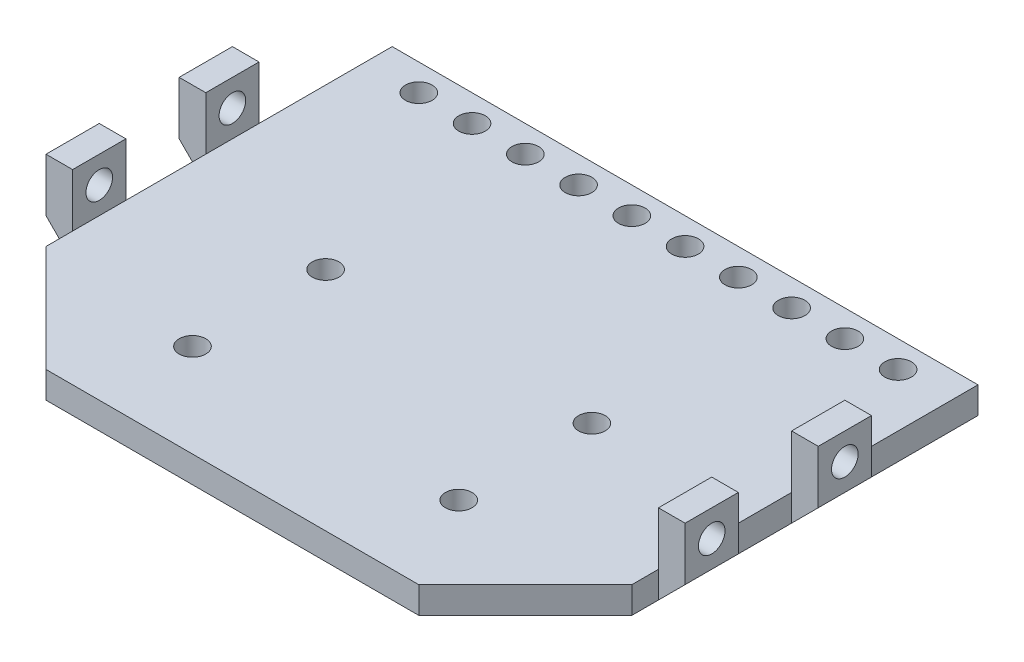
SolidWorks part; units mm, degrees
ref_plane "Front Plane" through (0, 0, 0) normal (0, 0, 1) x (1, 0, 0)
ref_plane "Top Plane" through (0, 0, 0) normal (0, 1, 0) x (1, 0, 0)
ref_plane "Right Plane" through (0, 0, 0) normal (1, 0, 0) x (0, 0, -1)
sketch "Sketch1" plane through (0, 0, 0) normal (0, 1, 0) x (1, 0, 0)
  line L1 (-60, 42.5) -> (60, 42.5)
  line L2 (-60, 42.5) -> (-60, -42.5)
  line L3 (-60, -42.5) -> (60, -42.5)
  line L4 (60, 42.5) -> (60, -42.5)
  line L5 (-60, 42.5) -> (60, -42.5) construction
  line L6 (-60, -42.5) -> (60, 42.5) construction
  point P0 (0, 0)
  dimension "D1" = 120
  dimension "D2" = 85
extrude "Boss-Extrude1" add sketch "Sketch1" along normal blind 5
sketch "Sketch2" plane through (0, 5, 0) normal (0, 1, 0) x (1, 0, 0)
  line L0 (-60, 42.5) -> (-60, -42.5) construction
  line L1 (-60, 17.5) -> (-55, 17.5)
  line L2 (-60, 17.5) -> (-60, 7.5)
  line L3 (-60, 7.5) -> (-55, 7.5)
  line L4 (-55, 17.5) -> (-55, 7.5)
  line L6 (-60, -7.5) -> (-55, -7.5)
  line L7 (-60, -7.5) -> (-60, -17.5)
  line L8 (-60, -17.5) -> (-55, -17.5)
  line L9 (-55, -7.5) -> (-55, -17.5)
  line L10 (-60, 12.5) -> (-55, 12.5) construction
  line L11 (-60, -12.5) -> (-55, -12.5) construction
  line L14 (60, 42.5) -> (-60, 42.5) construction
  line L16 (0, 0) -> (0, -27.3364) construction
  line L17 (60, -12.5) -> (55, -12.5) construction
  line L18 (60, 12.5) -> (55, 12.5) construction
  line L19 (55, -7.5) -> (55, -17.5)
  line L20 (60, -17.5) -> (55, -17.5)
  line L21 (60, -7.5) -> (60, -17.5)
  line L22 (60, -7.5) -> (55, -7.5)
  line L23 (55, 17.5) -> (55, 7.5)
  line L24 (60, 7.5) -> (55, 7.5)
  line L25 (60, 17.5) -> (60, 7.5)
  line L26 (60, 17.5) -> (55, 17.5)
  dimension "D1" = 30
  dimension "D2" = 10
  dimension "D3" = 10
  dimension "D4" = 25
  dimension "D5" = 5
  dimension "D6" = 5
extrude "Boss-Extrude2" add sketch "Sketch2" along normal blind 10
sketch "Sketch3" plane through (-60, 0, 0) normal (-1, 0, 0) x (0, 0, 1)
  line L0 (7.5, 15) -> (17.5, 15) construction
  line L1 (-17.5, 15) -> (-7.5, 15) construction
  line L2 (-17.5, 15) -> (-17.5, 5) construction
  line L3 (7.5, 15) -> (7.5, 5) construction
  circle A0 centre (-12.5, 10) radius 2.5
  circle A1 centre (12.5, 10) radius 2.5
  dimension "D1" = 5
  dimension "D2" = 5
  dimension "D3" = 5
  dimension "D4" = 5
  dimension "D5" = 5
  dimension "D6" = 5
extrude "Cut-Extrude1" cut sketch "Sketch3" against normal through all
sketch "Sketch5" plane through (0, 5, 0) normal (0, 1, 0) x (1, 0, 0)
  line L0 (0, 0) -> (0, -37.502) construction
  line L1 (-60, 42.5) -> (-55, 42.5)
  line L2 (-60, 42.5) -> (-60, 17.5)
  line L3 (-60, 17.5) -> (-55, 17.5)
  line L4 (-55, 42.5) -> (-55, 17.5)
  line L5 (-60, 7.5) -> (-55, 7.5)
  line L6 (-60, 7.5) -> (-60, -7.5)
  line L7 (-60, -7.5) -> (-55, -7.5)
  line L8 (-55, 7.5) -> (-55, -7.5)
  line L9 (-55, -17.5) -> (-60, -17.5)
  line L10 (-55, -17.5) -> (-55, -42.5)
  line L11 (-55, -42.5) -> (-60, -42.5)
  line L12 (-60, -17.5) -> (-60, -42.5)
  line L13 (60, -17.5) -> (60, -42.5)
  line L14 (55, -42.5) -> (60, -42.5)
  line L15 (55, -17.5) -> (55, -42.5)
  line L16 (55, -17.5) -> (60, -17.5)
  line L17 (55, 7.5) -> (55, -7.5)
  line L18 (60, -7.5) -> (55, -7.5)
  line L19 (60, 7.5) -> (60, -7.5)
  line L20 (60, 7.5) -> (55, 7.5)
  line L21 (55, 42.5) -> (55, 17.5)
  line L22 (60, 17.5) -> (55, 17.5)
  line L23 (60, 42.5) -> (60, 17.5)
  line L24 (60, 42.5) -> (55, 42.5)
extrude "Cut-Extrude2" cut sketch "Sketch5" against normal through all
chamfer "Chamfer1" distance 5 angle 45 4 edges at (-60, 0, 12.5) (-60, 0, -12.5) (60, 0, -12.5) (60, 0, 12.5)
sketch "Sketch6" plane through (0, 0, 0) normal (0, -1, 0) x (1, 0, 0)
  line L0 (-55, 42.5) -> (55, 42.5) construction
  circle A0 centre (25, 0) radius 2.5
  circle A1 centre (-25, 0) radius 2.5
  circle A2 centre (25, 25) radius 2.5
  circle A3 centre (-25, 25) radius 2.5
  dimension "D1" = 5
  dimension "D2" = 5
  dimension "D3" = 25
  dimension "D4" = 25
  dimension "D5" = 42.5
  dimension "D6" = 42.5
  dimension "D7" = 2
extrude "Cut-Extrude3" cut sketch "Sketch6" against normal through all
sketch "Sketch7" plane through (0, 0, 0) normal (0, -1, 0) x (1, 0, 0)
  line L0 (55, -42.5) -> (-55, -42.5) construction
  line L1 (-55, -17.5) -> (-55, -42.5) construction
  line L3 (55, -42.5) -> (55, -17.5) construction
  circle A0 centre (-45, -37.5) radius 2.5
  circle A1 centre (-35, -37.5) radius 2.5
  circle A2 centre (-25, -37.5) radius 2.5
  circle A3 centre (-15, -37.5) radius 2.5
  circle A4 centre (-5, -37.5) radius 2.5
  circle A5 centre (5, -37.5) radius 2.5
  circle A6 centre (15, -37.5) radius 2.5
  circle A7 centre (25, -37.5) radius 2.5
  circle A8 centre (35, -37.5) radius 2.5
  circle A9 centre (45, -37.5) radius 2.5
  dimension "D1" = 5
  dimension "D2" = 5
  dimension "D3" = 10
  dimension "D5" = 10
  dimension "D4" = 10
extrude "Cut-Extrude4" cut sketch "Sketch7" against normal blind 10
chamfer "Chamfer2" distance 20 angle 45 2 edges at (55, 2.5, 42.5) (-55, 2.5, 42.5)
